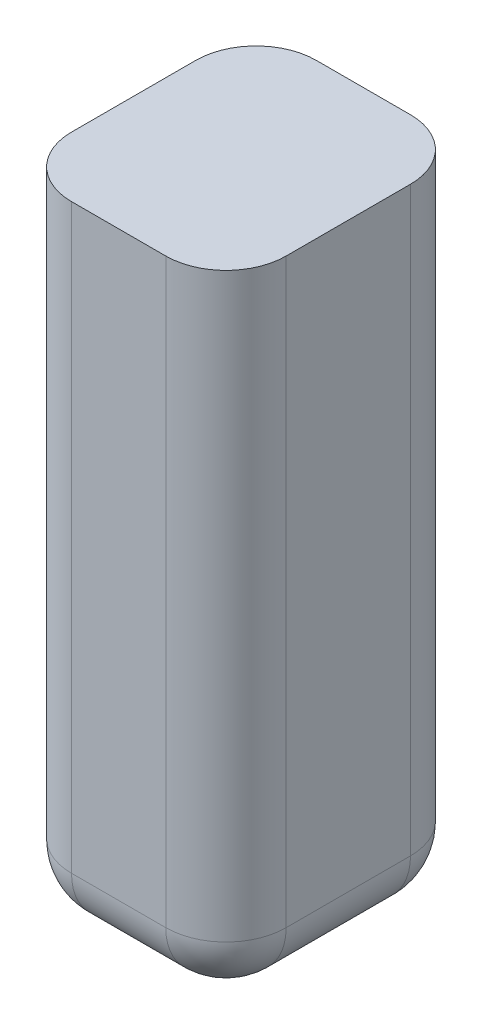
SolidWorks part; units mm, degrees
ref_plane "Front Plane" through (0, 0, 0) normal (0, 0, 1) x (1, 0, 0)
ref_plane "Top Plane" through (0, 0, 0) normal (0, 1, 0) x (1, 0, 0)
ref_plane "Right Plane" through (0, 0, 0) normal (1, 0, 0) x (0, 0, -1)
sketch "Sketch1" plane through (0, 0, 0) normal (0, 1, 0) x (1, 0, 0)
  line L0 (-2.675, 3.05) -> (2.675, 3.05)
  line L1 (-0.675, -1.05) -> (0.675, -1.05)
  line L2 (-0.675, -1.05) -> (-0.675, 1.05)
  line L3 (-0.675, 1.05) -> (0.675, 1.05)
  line L4 (0.675, -1.05) -> (0.675, 1.05)
  line L5 (-0.675, -1.05) -> (0.675, 1.05) construction
  line L6 (-0.675, 1.05) -> (0.675, -1.05) construction
  line L7 (2.675, -3.05) -> (2.675, 3.05)
  line L8 (-2.675, -3.05) -> (2.675, -3.05)
  line L9 (-2.675, -3.05) -> (-2.675, 3.05)
  point P0 (0, 0)
  dimension "D1" = 1.35
  dimension "D2" = 2.1
  dimension "D3" = 2
extrude "Boss-Extrude1" add sketch "Sketch1" along normal blind 6
sketch "Sketch2" plane through (0, 6, 0) normal (0, 1, 0) x (1, 0, 0)
  line L4 (-2.675, 3.05) -> (-2.675, -3.05)
  line L5 (-2.675, -3.05) -> (2.675, -3.05)
  line L6 (2.675, -3.05) -> (2.675, 3.05)
  line L7 (2.675, 3.05) -> (-2.675, 3.05)
  line L8 (-2.675, 3.05) -> (-2.675, -3.05)
  line L9 (-2.675, -3.05) -> (2.675, -3.05)
  line L10 (2.675, -3.05) -> (2.675, 3.05)
  line L11 (2.675, 3.05) -> (-2.675, 3.05)
  dimension "D1" = 0
extrude "Boss-Extrude2" add sketch "Sketch2" along normal blind 10
fillet "Fillet1" radius 1.5 4 edges at (-2.675, 0, 0) (0, 0, -3.05) (2.675, 0, 0) (0, 0, 3.05)
fillet "Fillet2" radius 1.5 8 edges at (-2.2357, 0.4393, -2.6107) (2.2357, 0.4393, -2.6107) (-2.2357, 0.4393, 2.6107) (2.2357, 0.4393, 2.6107) (-2.675, 8.75, -3.05) (2.675, 8.75, -3.05) (-2.675, 8.75, 3.05) (2.675, 8.75, 3.05)
